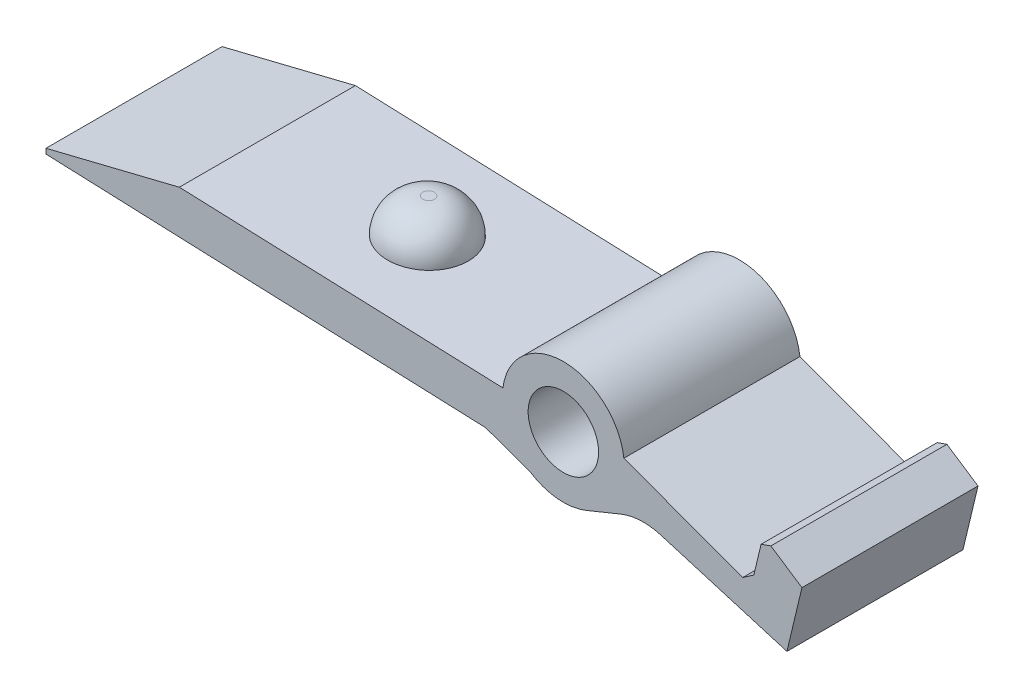
SolidWorks part; units mm, degrees
ref_plane "Front Plane" through (0, 0, 0) normal (0, 0, 1) x (1, 0, 0)
ref_plane "Top Plane" through (0, 0, 0) normal (0, 1, 0) x (1, 0, 0)
ref_plane "Right Plane" through (0, 0, 0) normal (1, 0, 0) x (0, 0, -1)
sketch "Sketch1" plane through (0, 0, 0) normal (0, 0, 1) x (1, 0, 0)
  line L0 (12.7417, -7.5) -> (13.4469, -7.5) construction
  line L3 (13.4469, -7.5) -> (13.4469, -7.2129) construction
  line L10 (17.8812, -7.2644) -> (12.8205, -5.3927)
  line L11 (20.2456, -9.1911) -> (13.5219, -7.1823)
  line L13 (-11.7974, -6.4827) -> (-11.7974, -5.3622)
  line L14 (-11.7974, -5.3622) -> (-11.1133, -4.6781)
  line L18 (18.3567, -6.9338) -> (17.8812, -7.2644)
  line L19 (18.5804, -5.5694) -> (19.095, -5.3882) construction
  line L20 (20.2456, -9.1911) -> (20.8493, -6.6686)
  line L22 (20.9629, -6.6239) -> (20.1487, -10.0251) construction
  line L23 (20.8493, -6.6686) -> (19.0813, -5.499)
  line L25 (19.095, -5.3882) -> (20.9629, -6.6239) construction
  line L28 (11.2217, -8.1189) -> (13.5219, -7.1823)
  line L29 (18.3567, -6.9338) -> (18.665, -5.6457)
  line L30 (18.665, -5.6457) -> (19.0813, -5.499)
  line L31 (18.2484, -6.9564) -> (18.5804, -5.5694) construction
  line L34 (13.4469, -5.6244) -> (13.4469, 0) construction
  line L35 (8.8091, -7.8799) -> (6.9322, -7.2129)
  line L36 (6.9322, -7.2129) -> (-11.7974, -6.4827)
  line L37 (-11.1133, -4.6781) -> (7.6653, -5.3771)
  circle A1 centre (10.2419, -5.7123) radius 1.5
  arc A8 (8.8091, -7.8799) -> (11.2217, -8.1189) centre (10.2419, -5.7123) ccw
  arc A9 (12.8205, -5.3927) -> (7.6653, -5.3771) centre (10.2419, -5.7123) ccw
  point P24 (18.8377, -5.4788)
  dimension "D1" = 3
  dimension "D2" = 0.1
  dimension "D3" = 0.1
  dimension "D4" = 0.1
  dimension "D5" = 0
  dimension "D6" = 0.1
extrude "Boss-Extrude1" add sketch "Sketch1" along normal blind 7.5
sketch "Sketch2" plane through (0, 0, 7.5) normal (0, 0, 1) x (1, 0, 0)
  line L0 (18.8464, -5.4824) -> (20.1267, -5.7059)
  line L1 (19.1138, -3.9507) -> (18.4942, -7.5) construction
  line L2 (20.1267, -5.7059) -> (20.6551, -6.6948)
  line L3 (20.1907, -9.4299) -> (20.9126, -5.1781) construction
  line L4 (20.6551, -6.6948) -> (20.9126, -5.1781)
  line L5 (20.9126, -5.1781) -> (20.3708, -4.1642)
  line L6 (20.3708, -4.1642) -> (19.1138, -3.9507)
  line L7 (20.3708, -4.1642) -> (19.1138, -3.9507) construction
  line L8 (19.1138, -3.9507) -> (18.8464, -5.4824)
fillet "Fillet1" radius 2.54 1 edges at (13.5219, -7.1823, 3.75)
chamfer "Chamfer2" distance 5 angle 16 1 edges at (-11.1133, -4.6781, 3.75)
sketch "Sketch4" plane through (-0.1893, -5.0848, 0) normal (0.0372, 0.9993, 0) x (0.9993, -0.0372, 0)
  circle A0 centre (0.8855, -3.75) radius 1.75
  dimension "D1" = 3.5
extrude "Boss-Extrude2" add sketch "Sketch4" along normal blind 1.5
fillet "Fillet2" radius 1.5 1 edges at (-0.9974, -3.5536, 3.75)
sketch "Sketch5" plane through (0, 0, 7.5) normal (0, 0, 1) x (1, 0, 0)
  line L0 (20.4055, -6.375) -> (19.7657, -9.0477)
  line L1 (20.8493, -6.6686) -> (19.0813, -5.499) construction
  line L2 (14.3786, -7.4383) -> (20.2456, -9.1911) construction
  line L3 (20.2456, -9.1911) -> (20.8493, -6.6686) construction
  line L4 (20.4055, -6.375) -> (20.8493, -6.6686)
  line L5 (20.8493, -6.6686) -> (20.2456, -9.1911)
  line L6 (20.2456, -9.1911) -> (19.7657, -9.0477)
  dimension "D1" = 0.5
extrude "Cut-Extrude1" cut sketch "Sketch5" against normal up to vertex (7.5 mm away)
